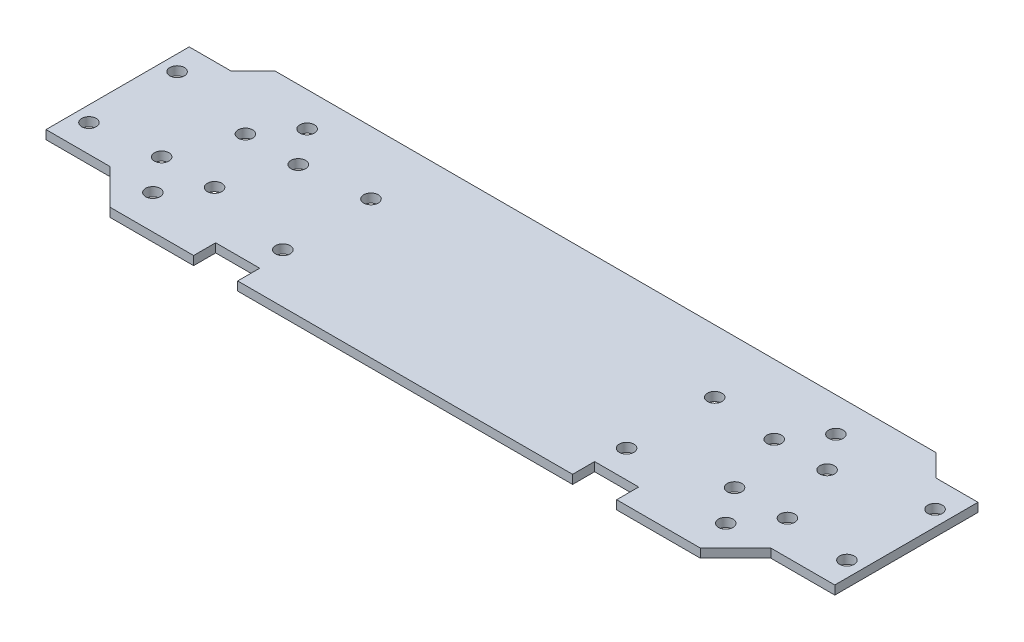
SolidWorks part; units mm, degrees
ref_plane "前视基准面" through (0, 0, 0) normal (0, 0, 1) x (1, 0, 0)
ref_plane "上视基准面" through (0, 0, 0) normal (0, 1, 0) x (1, 0, 0)
ref_plane "右视基准面" through (0, 0, 0) normal (1, 0, 0) x (0, 0, -1)
sketch "草图1" plane through (0, 0, 0) normal (0, 1, 0) x (1, 0, 0)
  line L1 (-75, -22.75) -> (75, -22.75)
  line L2 (-75, -22.75) -> (-75, 22.75)
  line L3 (-75, 22.75) -> (75, 22.75)
  line L4 (75, -22.75) -> (75, 22.75)
  line L5 (-75, -22.75) -> (75, 22.75) construction
  line L6 (-75, 22.75) -> (75, -22.75) construction
  point P0 (0, 0)
  dimension "D1" = 45.5
  dimension "D2" = 150
extrude "凸台-拉伸1" add sketch "草图1" along normal blind 2
sketch "草图2" plane through (0, 2, 0) normal (0, 1, 0) x (1, 0, 0)
  line L0 (-60, -11) -> (-65, -11) construction
  line L1 (-60, -11) -> (60, -11) construction
  line L2 (-60, -11) -> (-60, 11) construction
  line L3 (-60, 11) -> (60, 11) construction
  line L4 (60, -11) -> (60, 11) construction
  line L5 (-60, -11) -> (60, 11) construction
  line L6 (-60, 11) -> (60, -11) construction
  line L11 (-75, 22.75) -> (-75, -22.75) construction
  line L12 (-66, 7) -> (-54, 7) construction
  line L13 (-71, -15) -> (-59, -15) construction
  line L14 (-66, 7) -> (-66, 15) construction
  line L15 (-66, 15) -> (-54, 15) construction
  line L16 (-54, 7) -> (-54, 15) construction
  line L17 (-66, 7) -> (-54, 15) construction
  line L18 (-66, 15) -> (-54, 7) construction
  line L19 (-71, -15) -> (-71, -7) construction
  line L20 (-71, -7) -> (-59, -7) construction
  line L21 (-59, -15) -> (-59, -7) construction
  line L22 (-71, -15) -> (-59, -7) construction
  line L23 (-71, -7) -> (-59, -15) construction
  circle A4 centre (-60, 15) radius 1.65
  circle A5 centre (-66, 7) radius 1.65
  circle A6 centre (-54, 7) radius 1.65
  circle A7 centre (-71, -7) radius 1.65
  circle A8 centre (-59, -7) radius 1.65
  circle A9 centre (-65, -15) radius 1.65
  point P0 (0, 0)
  point P14 (-60, 0)
  dimension "D5" = 3.3
  dimension "D1" = 12
  dimension "D2" = 8
  dimension "D3" = 15
  dimension "D4" = 15
  dimension "D6" = 5
  dimension "D7" = 8
  dimension "D8" = 12
extrude "切除-拉伸1" cut sketch "草图2" against normal up to next
sketch "草图4" plane through (0, 2, 0) normal (0, 1, 0) x (1, 0, 0)
  line L0 (-75, -22.75) -> (75, -22.75) construction
  line L2 (-75, 22.75) -> (-75, -22.75) construction
  line L3 (-38, -22.75) -> (-48, -22.75)
  line L4 (-38, -22.75) -> (-38, -17.75)
  line L5 (-38, -17.75) -> (-48, -17.75)
  line L6 (-48, -22.75) -> (-48, -17.75)
  dimension "D1" = 27
  dimension "D2" = 10
  dimension "D3" = 5
extrude "切除-拉伸2" cut sketch "草图4" against normal up to next
mirror "镜向1" about plane through (0, 0, 0) normal (1, 0, 0) of "切除-拉伸2", "切除-拉伸1"
chamfer "倒角1" distance 8 angle 45 2 edges at (75, 1, 22.75) (-75, 1, 22.75)
sketch "草图6" plane through (0, 0, 0) normal (0, 1, 0) x (1, 0, 0)
  line L0 (75, 22.75) -> (-75, 22.75) construction
  line L1 (-75, -14.75) -> (-89.5, -14.75)
  line L2 (-75, -14.75) -> (-75, 17.75)
  line L3 (-75, 17.75) -> (-89.5, 17.75)
  line L4 (-89.5, -14.75) -> (-89.5, 17.75)
  dimension "D1" = 14.5
  dimension "D2" = 5
extrude "凸台-拉伸2" add sketch "草图6" along normal up to surface (2 mm away) up to face at (-65, 2, 16.65)
sketch "草图7" plane through (0, 2, 0) normal (0, 1, 0) x (1, 0, 0)
  line L0 (-89.5, 1.5) -> (-86, 1.5) construction
  line L1 (-89.5, -14.75) -> (-89.5, 17.75) construction
  line L2 (-86, 11.5) -> (-86, -8.5) construction
  line L3 (-59, -7) -> (-39, -7) construction
  line L4 (-39, -7) -> (-39, -11.5) construction
  line L5 (-39, -7) -> (-39, 8.5) construction
  circle A0 centre (-86, -8.5) radius 1.65
  circle A1 centre (-86, 11.5) radius 1.65
  circle A2 centre (-39, -11.5) radius 1.65
  circle A3 centre (-39, 8.5) radius 1.65
  point P7 (-86, 1.5)
  dimension "D3" = 3.3
  dimension "D1" = 3.5
  dimension "D2" = 20
  dimension "D4" = 20
  dimension "D5" = 4.5
  dimension "D6" = 20
extrude "切除-拉伸3" cut sketch "草图7" against normal up to next
mirror "镜向3" about plane through (0, 0, 0) normal (1, 0, 0) of "切除-拉伸3", "凸台-拉伸2"
chamfer "倒角2" distance 5 angle 45 2 edges at (-75, 1, -17.75) (75, 1, -17.75)
